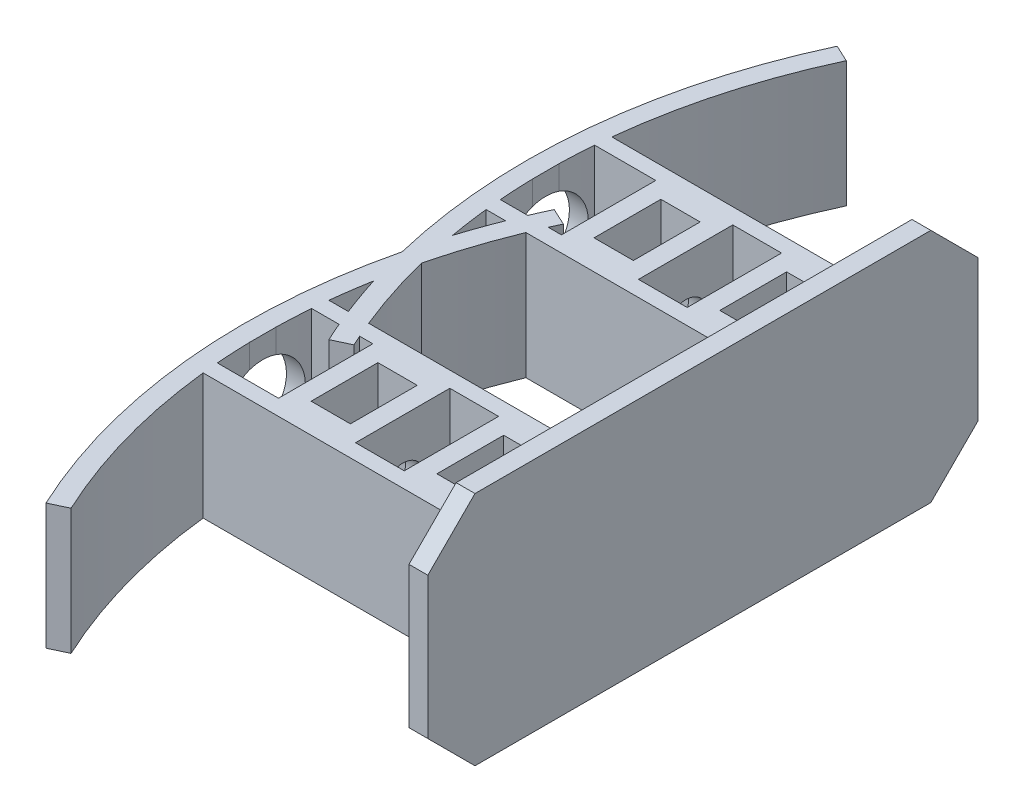
SolidWorks part; units mm, degrees
material "ABS"
ref_plane "Front Plane" through (0, 0, 0) normal (0, 0, 1) x (1, 0, 0)
ref_plane "Top Plane" through (0, 0, 0) normal (0, 1, 0) x (1, 0, 0)
ref_plane "Right Plane" through (0, 0, 0) normal (1, 0, 0) x (0, 0, -1)
sketch "Sketch1" plane through (0, 0, 0) normal (0, 0, 1) x (1, 0, 0)
  line L1 (-17, -8) -> (23, -8)
  line L2 (-17, -8) -> (-17, 8)
  line L3 (-17, 8) -> (23, 8)
  line L4 (23, -8) -> (23, 8)
  dimension "D1" = 40
  dimension "D2" = 16
  dimension "D3" = 8
  dimension "D4" = 17
extrude "Boss-Extrude1" add sketch "Sketch1" along normal blind 8 and the other way blind 8
shell "Shell1" thickness 2 removed face at (3, 8, 0)
sketch "Sketch3" plane through (-17, 0, 0) normal (-1, 0, 0) x (0, 0, 1)
  circle A0 centre (0, 0) radius 4.4706
extrude "Cut-Extrude1" cut sketch "Sketch3" against normal blind 10
ref_plane "Plane1" through (-7, 0, 0) normal (1, 0, 0) x (0, 0, -1)
sketch "Sketch4" plane through (-7, 0, 0) normal (1, 0, 0) x (0, 0, -1)
  line L0 (6, -6) -> (-6, -6) construction
  line L1 (6, -6) -> (-6, -6)
  line L2 (6, -6) -> (6, 8)
  line L3 (6, 8) -> (-6, 8)
  line L4 (-6, -6) -> (-6, 8)
  line L5 (-6, 8) -> (-6, -6) construction
  line L6 (6, 8) -> (6, -6) construction
  line L7 (6, 8) -> (-6, 8) construction
  circle A0 centre (0, 0) radius 2.75
  dimension "D1" = 5.5
extrude "Boss-Extrude2" add sketch "Sketch4" along normal blind 2.4
pattern_linear "LPattern1" count 2 spacing 7.4 along (1, 0, 0) of "Boss-Extrude2"
pattern_linear "LPattern2" count 2 spacing 16 along (1, 0, 0) of "LPattern1"
sketch "Sketch6" plane through (16.4, 0, 0) normal (-1, 0, 0) x (0, 0, 1)
  line L0 (-4.25, 2.4537) -> (-4.25, 8)
  line L1 (0, -4.9075) -> (4.25, -2.4537)
  line L2 (4.25, -2.4537) -> (4.25, 2.4537)
  line L5 (-4.25, 2.4537) -> (-4.25, -2.4537)
  line L6 (-4.25, -2.4537) -> (0, -4.9075)
  line L7 (-4.25, 8) -> (-6, 8)
  line L8 (-6, 8) -> (-6, -6)
  line L9 (-6, -6) -> (6, -6)
  line L10 (6, -6) -> (6, 8)
  line L11 (6, 8) -> (4.25, 8)
  line L12 (4.25, 8) -> (4.25, 2.4537)
  line L13 (6, 8) -> (6, -6) construction
  line L14 (0, 4.9075) -> (-2.125, 3.6806) [skipped]
  line L15 (4.25, 2.4537) -> (2.125, 3.6806) [skipped]
  line L16 (6, -6) -> (-6, -6) construction
  line L17 (-6, -6) -> (-6, 8) construction
  line L18 (-6, 8) -> (6, 8) construction
  circle A0 centre (0, 0) radius 4.25 construction
  dimension "D1" = 8.5
extrude "Boss-Extrude4" add sketch "Sketch6" along normal blind 5
pattern_linear "LPattern3" count 2 spacing 16 along (-1, 0, 0) of "Boss-Extrude4"
sketch "Sketch11" plane through (0, -8, 0) normal (0, -1, 0) x (1, 0, 0)
  line L0 (-10.252, -32.3303) -> (59.0805, 0) construction
  line L1 (59.0805, 0) -> (-10.252, 32.3303) construction
  line L2 (59.0805, 0) -> (-17, 0) construction
  line L3 (-10.252, -32.3303) -> (-8.0769, -31.316)
  line L4 (23, -8) -> (23, 8)
  line L5 (23, 8) -> (-17, 8)
  line L6 (-17, 8) -> (-17, -8)
  line L7 (-17, -8) -> (23, -8)
  line L8 (23, -8) -> (23, 8)
  line L9 (23, 8) -> (-17, 8)
  line L10 (-17, 8) -> (-17, -8)
  line L11 (-17, -8) -> (23, -8)
  line L12 (-8.0769, 31.316) -> (-10.252, 32.3303)
  arc A0 (-17, -8) -> (-17, 8) centre (59.0805, 0) cw construction
  arc A1 (-10.252, -32.3303) -> (-10.252, 32.3303) centre (59.0805, 0) cw
  arc A2 (-8.0769, -31.316) -> (-8.0769, 31.316) centre (59.0805, 0) cw
  line M11 (-17, 8) -> (-17, -8)
  line M12 (-17, -8) -> (23, -8)
  dimension "D2" = 76.5
  dimension "D3" = 50
  dimension "D4" = 25
  dimension "D1" = 0
  dimension "D5" = 2.4
extrude "Boss-Extrude6" add sketch "Sketch11" against normal up to surface (16 mm away) contours L9 A2 L12 A1 | A1 M11 | A2 L9 M12 M11 | L3 A2 A1 M12 region at (-13.1431, -8, -20.096) region at (-17.1678, -8, 0) region at (-15.9337, -8, 0) region at (-13.1431, -8, 20.096) up to face at (-2.1, 8, 0)
sketch "Sketch12" plane through (-7, 0, 0) normal (-1, 0, 0) x (0, 0, 1)
  circle A0 centre (0, 0) radius 5.25
  dimension "D1" = 10.5
extrude "Cut-Extrude3" cut sketch "Sketch12" along normal through all contours A0
pattern_linear "LPattern4" count 2 spacing 36 along (0, 0, -1) of bodies 116 109
sketch "Sketch8" plane through (23, 0, 0) normal (1, 0, 0) x (0, 0, -1)
  line L0 (28, 0) -> (8, 0) construction
  line L1 (47, -15) -> (-11, -15)
  line L2 (53, -9) -> (53, 9)
  line L3 (47, 15) -> (-11, 15)
  line L4 (-17, -9) -> (-17, 9)
  line L5 (28, -8) -> (28, 8) construction
  line L6 (8, -8) -> (8, 8) construction
  line L7 (53, -9) -> (47, -15)
  line L8 (53, 9) -> (47, 15)
  line L9 (-11, 15) -> (-17, 9)
  line L10 (-11, -15) -> (-17, -9)
  point P0 (53, -15)
  point P1 (-17, 15)
  point P2 (53, 15)
  point P3 (-17, -15)
  point P11 (18, 0)
  dimension "D1" = 30
  dimension "D2" = 70
  dimension "D3" = 15
  dimension "D4" = 35
extrude "Boss-Extrude5" add sketch "Sketch8" against normal blind 2.4
ref_plane "Plane2" through (0, 0, -18) normal (0, 0, -1) x (-1, 0, 0)
